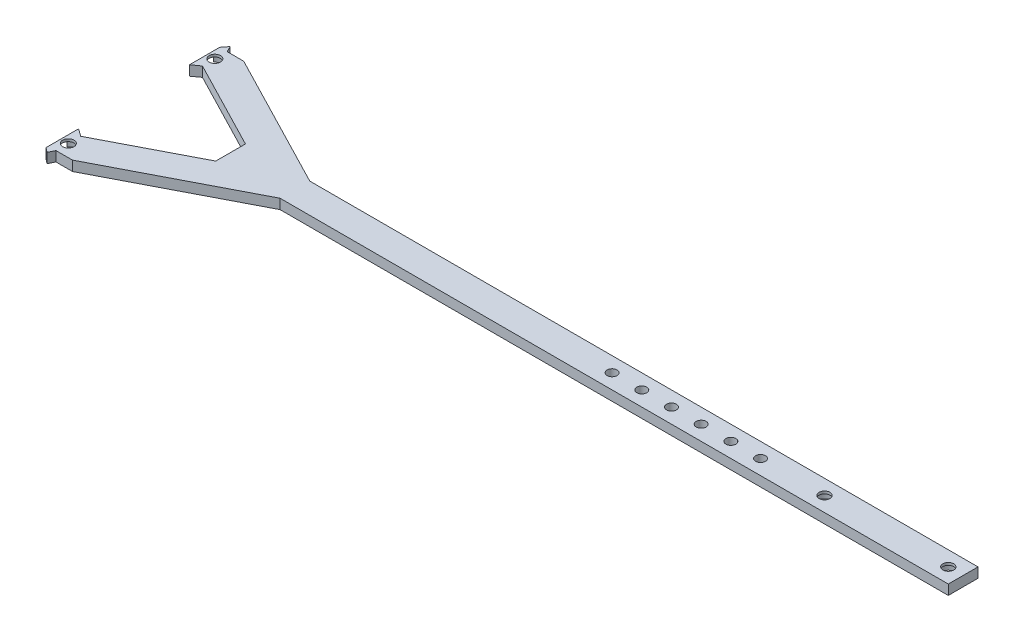
SolidWorks part; units mm, degrees
ref_plane "Płaszczyzna przednia" through (0, 0, 0) normal (0, 0, 1) x (1, 0, 0)
ref_plane "Płaszczyzna górna" through (0, 0, 0) normal (0, 1, 0) x (1, 0, 0)
ref_plane "Płaszczyzna prawa" through (0, 0, 0) normal (1, 0, 0) x (0, 0, -1)
sketch "Szkic1" plane through (0, -0.6011, 0) normal (0, -1, 0) x (1, 0, 0)
  line L0 (-40.95, 47.1335) -> (-28.6, 47.1335) construction
  line L1 (-28.6, 41.1335) -> (-40.95, 41.1335) construction
  line L2 (-159.9499, 47.1335) -> (-28.6, 47.1335)
  line L3 (-28.6, 41.1335) -> (-159.9499, 41.1335)
  line L4 (-28.6, 41.1335) -> (-11.9498, 41.1335)
  line L5 (-11.9498, 41.1335) -> (-11.9498, 47.1335)
  line L6 (-11.9498, 47.1335) -> (-28.6, 47.1335)
  line L7 (-159.9499, 41.1335) -> (-159.9499, 47.1335)
  circle A0 centre (-14.9498, 44.1337) radius 1.1 construction
  circle A1 centre (-39.9499, 44.1337) radius 1.1 construction
  circle A2 centre (-14.9498, 44.1337) radius 1.1
  circle A3 centre (-39.9499, 44.1337) radius 1.1
  dimension "D1" = 3
  dimension "D2" = 120
extrude "Dodanie-wyciągnięcie1" add sketch "Szkic1" along normal blind 2
sketch "Szkic2" plane through (0, -0.6011, 0) normal (0, 1, 0) x (1, 0, 0)
  line L0 (-177.9299, -26.8335) -> (-178.5249, -25.6335) construction
  line L1 (-179.4499, -32.9335) -> (-177.9299, -31.8335) construction
  line L2 (-178.5249, -62.6335) -> (-177.9299, -61.4335) construction
  line L3 (-177.9299, -56.4335) -> (-179.4499, -55.3335) construction
  line L4 (-177.9299, -26.8335) -> (-178.5249, -25.6335)
  line L5 (-179.4499, -32.9335) -> (-177.9299, -31.8335)
  line L6 (-178.5249, -62.6335) -> (-177.9299, -61.4335)
  line L7 (-177.9299, -56.4335) -> (-179.4499, -55.3335)
  line L8 (-178.5249, -25.6335) -> (-179.4499, -26.8335)
  line L9 (-179.4499, -26.8335) -> (-179.4499, -32.9335)
  line L10 (-178.5249, -62.6335) -> (-179.4499, -61.9205)
  line L11 (-179.4499, -61.9205) -> (-179.4499, -55.3335)
  line L12 (-177.9299, -26.8335) -> (-174.5965, -26.8335)
  line L13 (-174.5965, -26.8335) -> (-146.9499, -41.1335)
  line L14 (-159.9499, -41.1335) -> (-159.9499, -47.1335)
  line L15 (-159.9499, -41.1335) -> (-11.9498, -41.1335) construction
  line L16 (-174.5965, -61.4335) -> (-177.9299, -61.4335)
  line L18 (-146.9499, -47.1335) -> (-174.5965, -61.4335)
  line L19 (-11.9498, -47.1335) -> (-159.9499, -47.1335) construction
  line L20 (-177.9299, -56.4335) -> (-159.9499, -47.1335)
  line L21 (-159.9499, -41.1335) -> (-177.9299, -31.8335)
  line L22 (-146.9499, -41.1335) -> (-146.9499, -47.1335)
  circle A0 centre (-177.9297, -58.9335) radius 1.15 construction
  circle A1 centre (-177.9297, -29.3335) radius 1.15 construction
  circle A2 centre (-177.9297, -58.9335) radius 1.15
  circle A3 centre (-177.9297, -29.3335) radius 1.15
  circle A4 centre (-39.9499, -44.1337) radius 1.1 construction
  dimension "D1" = 107
extrude "Dodanie-wyciągnięcie3" add sketch "Szkic2" against normal blind 2
sketch "Szkic4" plane through (0, -2.6011, 0) normal (0, -1, 0) x (1, 0, 0)
  circle A0 centre (-14.9498, 44.1337) radius 2
  circle A1 centre (-39.9499, 44.1337) radius 2
  circle A2 centre (-177.9297, 58.9335) radius 2
  circle A3 centre (-177.9297, 29.3335) radius 2
  dimension "D1" = 4
extrude "Wytnij-wyciągnięcie2" cut sketch "Szkic4" against normal blind 1.5
sketch "Szkic6" plane through (0, -2.6011, 0) normal (0, -1, 0) x (1, 0, 0)
  line L0 (-158.1419, 44.1335) -> (-152.1419, 44.1335)
  line L1 (-146.9499, 41.1335) -> (-11.9498, 41.1335) construction
  arc A0 (-152.1419, 44.1335) -> (-158.1419, 44.1335) centre (-155.1419, 44.1335) ccw
  dimension "D1" = 6
  dimension "D2" = 3
revolve "Obrót11" add sketch "Szkic6" angle 180 about L0
sketch "Szkic7" plane through (0, -0.6011, 0) normal (0, 1, 0) x (1, 0, 0)
  line L0 (-146.9499, -41.1335) -> (-11.9498, -41.1335) construction
  circle A0 centre (-52.8732, -44.1335) radius 1
  circle A1 centre (-58.8732, -44.1335) radius 1
  circle A2 centre (-64.8732, -44.1335) radius 1
  circle A3 centre (-70.8732, -44.1335) radius 1
  circle A4 centre (-76.8732, -44.1335) radius 1
  circle A5 centre (-82.8732, -44.1335) radius 1
  point P12 (0, 0)
  point P13 (-52.8732, -44.1571)
  dimension "D2" = 2
  dimension "D1" = 3
  dimension "D3" = 6
  dimension "D4" = 6
  dimension "D5" = 6
  dimension "D6" = 6
  dimension "D7" = 6
extrude "Wytnij-wyciągnięcie3" cut sketch "Szkic7" against normal blind 3
